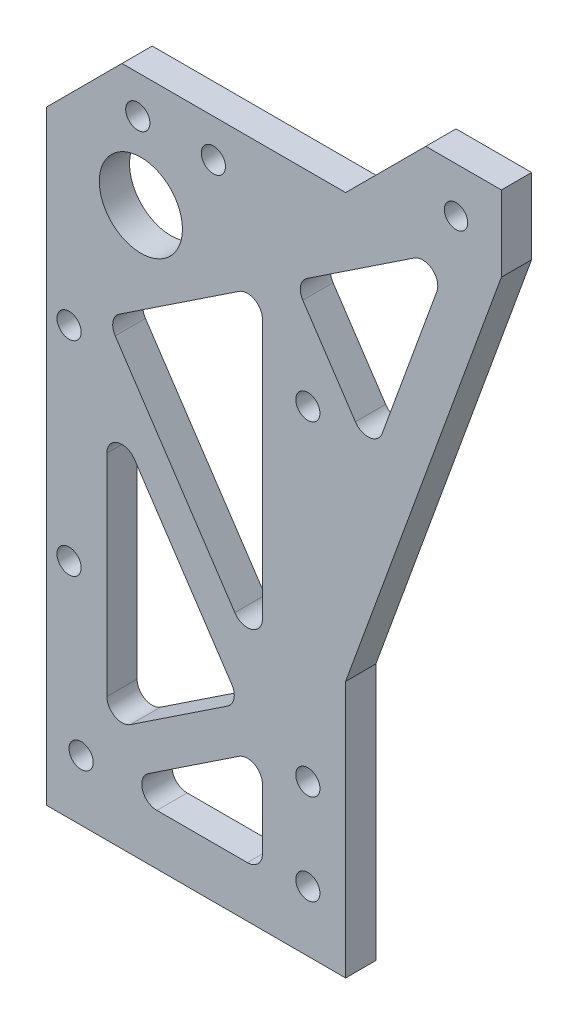
SolidWorks part; units mm, degrees
ref_plane "前视基准面" through (0, 0, 0) normal (0, 0, 1) x (1, 0, 0)
ref_plane "上视基准面" through (0, 0, 0) normal (0, 1, 0) x (1, 0, 0)
ref_plane "右视基准面" through (0, 0, 0) normal (1, 0, 0) x (0, 0, -1)
ref_plane "基准面1" through (0, 0, 4) normal (0, 0, 1) x (1, 0, 0)
sketch "草图1" plane through (0, 0, 4) normal (0, 0, 1) x (1, 0, 0)
  line L0 (27.5, -75) -> (27.5, -38.0701)
  line L1 (-12.0937, 15) -> (-12.0937, -75)
  line L2 (-12.0937, 15) -> (27.5, 15)
  line L3 (27.5, 15) -> (27.5, -38.0701)
  line L6 (-12.0937, -75) -> (27.5, -75)
  circle A0 centre (22.5, -12) radius 1.6
  circle A1 centre (22.5, -55) radius 1.6
  circle A2 centre (22.5, -67) radius 1.6
  circle A3 centre (-7.5, -67) radius 1.6
  circle A4 centre (-9.0937, -18.5) radius 1.6
  circle A5 centre (0.4063, 0) radius 6.075
  circle A6 centre (-9.0937, -45.5) radius 1.6
  circle A7 centre (0, 10) radius 1.6
  dimension "D3" = 3.2
  dimension "D4" = 3.2
  dimension "D6" = 12.5
  dimension "D14" = 27
  dimension "D16" = 5
  dimension "D19" = 8
  dimension "D21" = 15
  dimension "D18" = 30
  dimension "D23" = 12.15
  dimension "D2" = 90
  dimension "D12" = 3
  dimension "D13" = 3
  dimension "D15" = 5
  dimension "D17" = 5
  dimension "D20" = 8
  dimension "D22" = 27
extrude "凸台-拉伸1" add sketch "草图1" against normal blind 4
sketch "草图2" plane through (0, 0, 4) normal (0, 0, 1) x (1, 0, 0)
  circle A1 centre (10, 10) radius 1.6
  circle A2 centre (0, 10) radius 1.6 construction
  dimension "D1" = 3.2
  dimension "D2" = 10
extrude "切除-拉伸1" cut sketch "草图2" against normal up to next
sketch "草图3" plane through (0, 0, 4) normal (0, 0, 1) x (1, 0, 0)
  line L3 (38.1066, 25.6066) -> (48.1066, 25.6066)
  line L4 (48.1066, 25.6066) -> (48.1066, 15.6066)
  line L6 (27.5, 15) -> (38.1066, 25.6066)
  line L10 (48.1066, 15.6066) -> (27.5, -41.0096)
  line L11 (27.5, 15) -> (27.5, -41.0096)
  line L13 (27.5, -75) -> (27.5, 15) construction
  line L15 (27.5, 15) -> (-12.0937, 15) construction
  dimension "D1" = 135
  dimension "D2" = 160
  dimension "D3" = 10
  dimension "D4" = 15
extrude "凸台-拉伸2" add sketch "草图3" against normal blind 4
sketch "草图5" plane through (0, 0, 4) normal (0, 0, 1) x (1, 0, 0)
  line L0 (48.1066, 25.6066) -> (38.1066, 25.6066) construction
  line L2 (48.1066, 15.6066) -> (48.1066, 25.6066) construction
  circle A0 centre (42.1066, 19.6066) radius 1.55
  dimension "D1" = 3.1
  dimension "D2" = 6
  dimension "D3" = 6
extrude "切除-拉伸2" cut sketch "草图5" against normal up to next
sketch "草图6" plane through (0, 0, 4) normal (0, 0, 1) x (1, 0, 0)
  circle A0 centre (0.4063, 0) radius 5.5
  circle A1 centre (0.4063, 0) radius 6.075
  circle A2 centre (0.4063, 0) radius 6.075 construction
  dimension "D1" = 12.15
  dimension "D2" = 11
extrude "凸台-拉伸3" add sketch "草图6" against normal blind 4
chamfer "倒角1" distance 10 angle 45 1 edges at (-12.0937, 15, 2)
sketch "草图7" plane through (0, 0, 4) normal (0, 0, 1) x (1, 0, 0)
  line L0 (13.3925, -3.3736) -> (-2.4283, -13.8941)
  line L1 (-2.9863, -16.6669) -> (12.8346, -40.4585)
  line L2 (16.5, -39.3511) -> (16.5, -5.039)
  line L3 (-4.0937, -30.6508) -> (-4.0937, -58.5424)
  line L4 (-0.9863, -60.2078) -> (11.8742, -51.6559)
  line L5 (12.4322, -48.883) -> (-0.4283, -29.5433)
  line L6 (13.3925, -56.6508) -> (1.4183, -64.6134)
  line L7 (2.5258, -68.2788) -> (14.5, -68.2788)
  line L8 (16.5, -66.2788) -> (16.5, -58.3162)
  line L9 (21.8337, -0.1623) -> (28.7861, -10.6174)
  line L10 (32.3309, -10.194) -> (39.5714, 9.6992)
  line L11 (36.5846, 12.0486) -> (22.3916, 2.6106)
  line L12 (27.5, -41.0096) -> (48.1066, 15.6066) construction
  line L13 (-12.0937, 5) -> (-12.0937, -75) construction
  line L14 (27.5, -75) -> (27.5, -41.0096) construction
  circle A0 centre (0.4063, 0) radius 5.5 construction
  circle A1 centre (22.5, -12) radius 1.6 construction
  arc A2 (28.7861, -10.6174) -> (32.3309, -10.194) centre (30.4515, -9.51) ccw
  arc A3 (39.5714, 9.6992) -> (36.5846, 12.0486) centre (37.692, 10.3832) ccw
  arc A4 (21.8337, -0.1623) -> (22.3916, 2.6106) centre (23.499, 0.9452) cw
  arc A5 (14.5, -68.2788) -> (16.5, -66.2788) centre (14.5, -66.2788) ccw
  arc A6 (13.3925, -56.6508) -> (16.5, -58.3162) centre (14.5, -58.3162) cw
  arc A7 (1.4183, -64.6134) -> (2.5258, -68.2788) centre (2.5258, -66.2788) ccw
  arc A8 (-4.0937, -58.5424) -> (-0.9863, -60.2078) centre (-2.0937, -58.5424) ccw
  arc A9 (-4.0937, -30.6508) -> (-0.4283, -29.5433) centre (-2.0937, -30.6508) cw
  arc A10 (11.8742, -51.6559) -> (12.4322, -48.883) centre (10.7668, -49.9905) ccw
  arc A11 (12.8346, -40.4585) -> (16.5, -39.3511) centre (14.5, -39.3511) ccw
  arc A12 (13.3925, -3.3736) -> (16.5, -5.039) centre (14.5, -5.039) cw
  arc A13 (-2.4283, -13.8941) -> (-2.9863, -16.6669) centre (-1.3209, -15.5595) ccw
  point P31 (20.7262, 1.5031)
  point P38 (-4.0937, -68.2788)
  point P47 (16.5, -45.9706)
  point P52 (-4.0937, -15.0015)
  dimension "D8" = 2
  dimension "D1" = 5
  dimension "D2" = 5
  dimension "D3" = 8
  dimension "D4" = 11
  dimension "D5" = 10
  dimension "D6" = 6
  dimension "D7" = 6
extrude "切除-拉伸3" cut sketch "草图7" against normal blind 10
